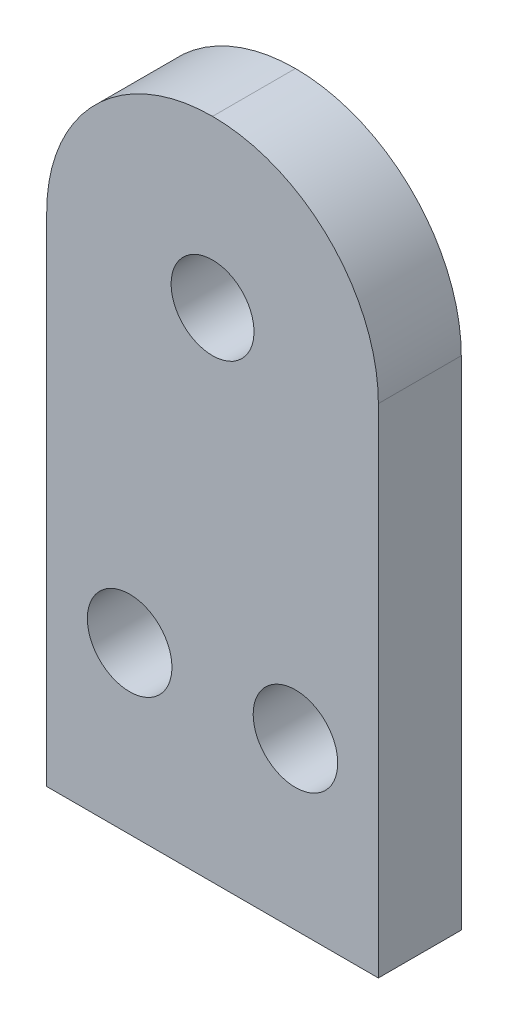
SolidWorks part; units mm, degrees
ref_plane "Front Plane" through (0, 0, 0) normal (0, 0, 1) x (1, 0, 0)
ref_plane "Top Plane" through (0, 0, 0) normal (0, 1, 0) x (1, 0, 0)
ref_plane "Right Plane" through (0, 0, 0) normal (1, 0, 0) x (0, 0, -1)
sketch "Sketch1" plane through (0, 0, 0) normal (0, 0, 1) x (1, 0, 0)
  line L1 (10, -20) -> (-10, -20)
  line L2 (10, -20) -> (10, 20)
  line L3 (10, 20) -> (-10, 20)
  line L4 (-10, -20) -> (-10, 20)
  line L5 (10, -20) -> (-10, 20) construction
  line L6 (10, 20) -> (-10, -20) construction
  point P0 (0, 0)
  dimension "D1" = 20
  dimension "D2" = 40
extrude "Boss-Extrude1" add sketch "Sketch1" along normal blind 5
fillet "Fillet2" radius 10 2 edges at (-10, 20, 2.5) (10, 20, 2.5)
sketch "Sketch2" plane through (0, 0, 0) normal (0, 0, -1) x (-1, 0, 0)
  circle A0 centre (0, 10) radius 2.5
  dimension "D1" = 5
extrude "Cut-Extrude1" cut sketch "Sketch2" against normal through all
sketch "Sketch3" plane through (0, 0, 0) normal (0, 0, -1) x (-1, 0, 0)
  line L0 (10, -20) -> (-10, -20) construction
  line L1 (10, 10) -> (10, -20) construction
  circle A0 centre (-5, -10) radius 2.55
  circle A1 centre (5, -10) radius 2.55
  dimension "D1" = 5.1
  dimension "D2" = 10
  dimension "D4" = 5.1
  dimension "D6" = 10
  dimension "D3" = 15
  dimension "D5" = 10
extrude "Cut-Extrude2" cut sketch "Sketch3" against normal blind 5
